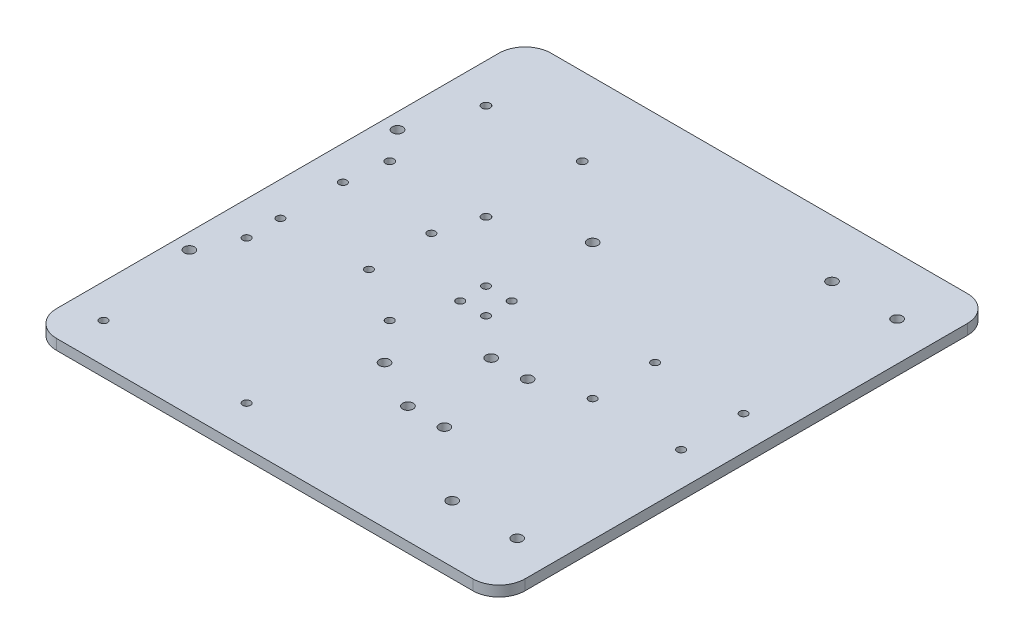
SolidWorks part; units mm, degrees
ref_plane "前视基准面" through (0, 0, 0) normal (0, 0, 1) x (1, 0, 0)
ref_plane "上视基准面" through (0, 0, 0) normal (0, 1, 0) x (1, 0, 0)
ref_plane "右视基准面" through (0, 0, 0) normal (1, 0, 0) x (0, 0, -1)
other "Configuration Table"
sketch "草图1" plane through (0, 0, 0) normal (0, 1, 0) x (1, 0, 0)
  line L1 (-90, -95) -> (90, -95)
  line L2 (-90, -95) -> (-90, 95)
  line L3 (-90, 95) -> (90, 95)
  line L4 (90, -95) -> (90, 95)
  line L5 (-90, -95) -> (90, 95) construction
  line L6 (-90, 95) -> (90, -95) construction
  point P0 (0, 0)
  dimension "D1" = 190
  dimension "D2" = 180
extrude "凸台-拉伸1" add sketch "草图1" along normal blind 4
sketch "草图2" plane through (0, 4, 0) normal (0, 1, 0) x (1, 0, 0)
  line L0 (90, -95) -> (90, 95) construction
  line L1 (66, -25) -> (85, -25) construction
  line L2 (66, -25) -> (66, 25) construction
  line L3 (66, 25) -> (85, 25) construction
  line L4 (85, -25) -> (85, 25) construction
  line L5 (66, -25) -> (85, 25) construction
  line L6 (66, 25) -> (85, -25) construction
  circle A0 centre (66, 25) radius 1.6
  circle A1 centre (66, -25) radius 1.6
  circle A2 centre (85, -25) radius 1.6
  circle A3 centre (85, 25) radius 1.6
  circle A7 centre (80.7, 7) radius 3
  point P0 (75.5, 0)
  dimension "D4" = 3.2
  dimension "D5" = 4.3
  dimension "D7" = 6
  dimension "D1" = 19
  dimension "D2" = 50
  dimension "D3" = 5
  dimension "D6" = 18
sketch "草图4" plane through (0, 4, 0) normal (0, 1, 0) x (1, 0, 0)
  line L0 (90, 95) -> (-90, 95) construction
  line L1 (-75, 65) -> (-38, 65) construction
  line L2 (-75, 65) -> (-75, 28) construction
  line L3 (-75, 28) -> (-38, 28) construction
  line L4 (-38, 65) -> (-38, 28) construction
  line L5 (-90, 95) -> (-90, -95) construction
  circle A0 centre (-75, 65) radius 1.6
  circle A1 centre (-38, 65) radius 1.6
  circle A2 centre (-38, 28) radius 1.6
  circle A3 centre (-75, 28) radius 1.6
  dimension "D4" = 3.2
  dimension "D1" = 37
  dimension "D2" = 30
  dimension "D3" = 15
extrude "切除-拉伸3" cut sketch "草图4" against normal blind 4
sketch "草图5" plane through (0, 4, 0) normal (0, 1, 0) x (1, 0, 0)
  line L5 (-90, 95) -> (-90, -95) construction
  line L7 (-22, -80) -> (-77, -80) construction
  line L8 (-22, -80) -> (-22, -25) construction
  line L9 (-22, -25) -> (-77, -25) construction
  line L10 (-77, -80) -> (-77, -25) construction
  line L11 (-90, -95) -> (90, -95) construction
  circle A8 centre (-77, -80) radius 1.5
  circle A9 centre (-77, -25) radius 1.5
  circle A10 centre (-22, -25) radius 1.5
  circle A11 centre (-22, -80) radius 1.5
  dimension "D2" = 3
  dimension "D1" = 55
  dimension "D3" = 13
  dimension "D4" = 15
extrude "切除-拉伸4" cut sketch "草图5" against normal blind 4
sketch "草图7" plane through (0, 0, 0) normal (0, -1, 0) x (1, 0, 0)
  line L0 (-90, 95) -> (90, 95) construction
  line L2 (90, 95) -> (90, -95) construction
  circle A0 centre (24, 50) radius 2
  circle A1 centre (10, 50) radius 2
  circle A2 centre (24, 18) radius 2
  circle A3 centre (10, 18) radius 2
  dimension "D2" = 4
  dimension "D5" = 4
  dimension "D1" = 80
  dimension "D3" = 45
  dimension "D6" = 14
  dimension "D7" = 32
extrude "切除-拉伸5" cut sketch "草图7" against normal blind 10
sketch "草图8" plane through (0, 0, 0) normal (0, -1, 0) x (1, 0, 0)
  line L1 (-14.9497, -4.9497) -> (-5.0503, -4.9497) construction
  line L2 (-14.9497, -4.9497) -> (-14.9497, 4.9497) construction
  line L3 (-14.9497, 4.9497) -> (-5.0503, 4.9497) construction
  line L4 (-5.0503, -4.9497) -> (-5.0503, 4.9497) construction
  line L5 (-14.9497, -4.9497) -> (-5.0503, 4.9497) construction
  line L6 (-14.9497, 4.9497) -> (-5.0503, -4.9497) construction
  circle A0 centre (-14.9497, 4.9497) radius 1.5
  circle A1 centre (-5.0503, 4.9497) radius 1.5
  circle A2 centre (-14.9497, -4.9497) radius 1.5
  circle A3 centre (-5.0503, -4.9497) radius 1.5
  point P0 (-10, 0)
  dimension "D4" = 3
  dimension "D1" = 14
  dimension "D3" = 10
extrude "切除-拉伸6" cut sketch "草图8" against normal blind 10
sketch "草图11" plane through (0, 0, 0) normal (0, -1, 0) x (1, 0, 0)
  line L0 (60, 95) -> (60, -95) construction
  line L1 (-90, 0) -> (90, 0) construction
  line L2 (90, 95) -> (90, -95) construction
  line L3 (-90, -95) -> (-90, 95) construction
  line L4 (90, -95) -> (-90, -95) construction
  line L5 (-90, 95) -> (90, 95) construction
  circle A0 centre (77, 12) radius 1.5
  circle A1 centre (43, 12) radius 1.5
  circle A2 centre (77, -12) radius 1.5
  circle A3 centre (43, -12) radius 1.5
  dimension "D1" = 3
  dimension "D2" = 24
  dimension "D3" = 34
  dimension "D4" = 30
extrude "切除-拉伸8" cut sketch "草图11" against normal blind 4
sketch "草图12" plane through (0, 0, 0) normal (0, -1, 0) x (1, 0, 0)
  line L0 (-90, -95) -> (-90, 95) construction
  line L1 (-9, -40) -> (-84, -40) construction
  line L2 (-9, -40) -> (-9, 40) construction
  line L3 (-9, 40) -> (-84, 40) construction
  line L4 (-84, -40) -> (-84, 40) construction
  line L5 (-9, -40) -> (-84, 40) construction
  line L6 (-9, 40) -> (-84, -40) construction
  circle A0 centre (-84, 40) radius 2
  circle A1 centre (-9, 40) radius 2
  circle A2 centre (-9, -40) radius 2
  circle A3 centre (-84, -40) radius 2
  point P0 (-46.5, 0)
  dimension "D4" = 4
  dimension "D1" = 6
  dimension "D2" = 75
  dimension "D3" = 80
extrude "切除-拉伸9" cut sketch "草图12" against normal blind 4
sketch "草图15" plane through (0, 4, 0) normal (0, 1, 0) x (1, 0, 0)
  line L1 (90, -95) -> (90, 95) construction
  line L2 (0, 0) -> (50000, 0) construction
  circle A0 centre (75, -73) radius 2
  circle A1 centre (50, -73) radius 2
  dimension "D2" = 4
  dimension "D5" = 4
  dimension "D1" = 73
  dimension "D3" = 15
  dimension "D4" = 25
extrude "切除-拉伸10" cut sketch "草图15" against normal through all
mirror "镜向2" about plane through (0, 0, 0) normal (0, 0, 1) of "切除-拉伸10"
fillet "圆角2" radius 10 4 edges at (-90, 2, 95) (90, 2, 95) (90, 2, -95) (-90, 2, -95)
mirror "镜向3" about plane through (0, 0, 0) normal (1, 0, 0) of "切除-拉伸8"
